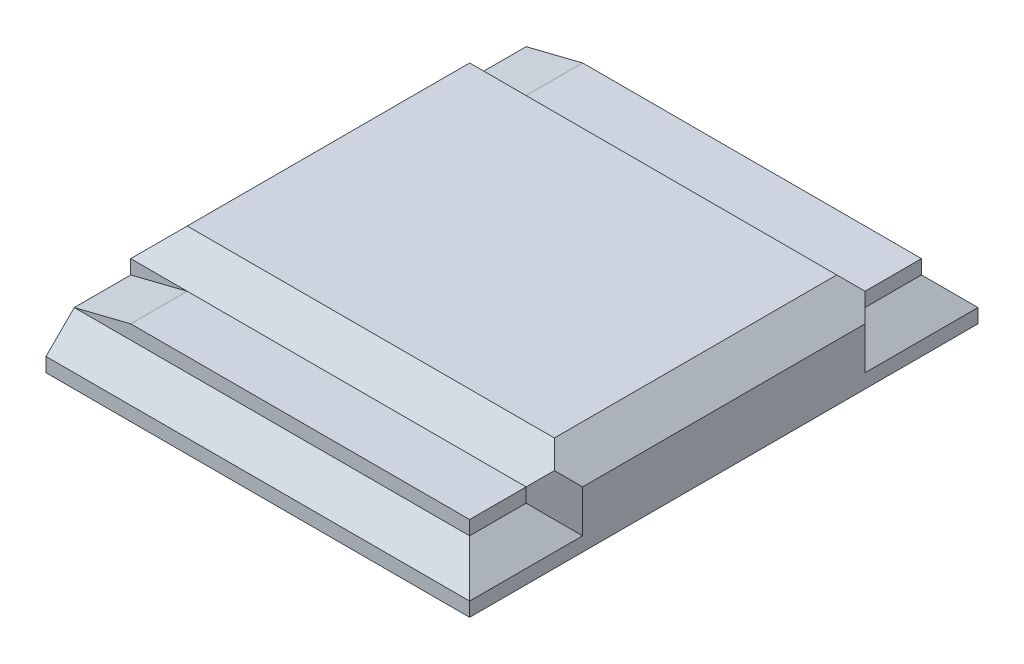
SolidWorks part; units mm, degrees
ref_plane "前视基准面" through (0, 0, 0) normal (0, 0, 1) x (1, 0, 0)
ref_plane "上视基准面" through (0, 0, 0) normal (0, 1, 0) x (1, 0, 0)
ref_plane "右视基准面" through (0, 0, 0) normal (1, 0, 0) x (0, 0, -1)
sketch "草图1" plane through (0, 0, 0) normal (0, 1, 0) x (1, 0, 0)
  line L1 (-9, -9) -> (9, -9)
  line L2 (-9, -9) -> (-9, 9)
  line L3 (-9, 9) -> (9, 9)
  line L4 (9, -9) -> (9, 9)
  line L5 (-9, -9) -> (9, 9) construction
  line L6 (-9, 9) -> (9, -9) construction
  point P0 (0, 0)
  dimension "D1" = 18
  dimension "D2" = 18
extrude "凸台-拉伸1" add sketch "草图1" along normal blind 1.5
chamfer "倒角1" distance 1 angle 45 2 edges at (0, 1.5, -9) (0, 1.5, 9)
sketch "草图2" plane through (0, 1.5, 0) normal (0, 1, 0) x (1, 0, 0)
  line L0 (-9, 8) -> (-9, -8) construction
  line L1 (9, -6) -> (-9, -6)
  line L2 (9, -6) -> (9, 6)
  line L3 (9, 6) -> (-9, 6)
  line L4 (-9, -6) -> (-9, 6)
  line L5 (9, -6) -> (-9, 6) construction
  line L6 (9, 6) -> (-9, -6) construction
  point P0 (0, 0)
  dimension "D1" = 12
extrude "凸台-拉伸2" add sketch "草图2" along normal blind 1.5
chamfer "倒角2" distance 1 angle 45 2 edges at (0, 3, -6) (0, 3, 6)
chamfer "倒角3" distance 1 angle 45 5 edges at (9, 1.75, 6) (9, 1.5, 7) (9, 1.75, -6) (9, 1.5, -7) (9, 3, 0)
sketch "草图9" plane through (-9, 0, 0) normal (-1, 0, 0) x (0, 0, 1)
  line L0 (-6, 1.5) -> (-6, 2)
  line L1 (-6, 2) -> (-5, 3)
  line L2 (-5, 3) -> (5, 3)
  line L3 (5, 3) -> (6, 2)
  line L4 (6, 2) -> (6, 1.5)
  line L5 (6, 1.5) -> (-6, 1.5)
extrude "切除-拉伸2" cut sketch "草图9" against normal blind 3
chamfer "倒角5" distance 1 angle 45 1 edges at (-6, 3, 0)
sketch "草图23" plane through (-9, 0, 0) normal (-1, 0, 0) x (0, 0, 1)
  line L6 (9, 0.5) -> (8, 1.5)
  line L7 (8, 1.5) -> (-8, 1.5)
  line L8 (-8, 1.5) -> (-9, 0.5)
  line L9 (-9, 0.5) -> (-9, 0)
  line L10 (-9, 0) -> (9, 0)
  line L11 (9, 0) -> (9, 0.5)
  line L12 (9, 0.5) -> (8, 1.5)
  line L13 (8, 1.5) -> (-8, 1.5)
  line L14 (-8, 1.5) -> (-9, 0.5)
  line L15 (-9, 0.5) -> (-9, 0)
  line L16 (-9, 0) -> (9, 0)
  line L17 (9, 0) -> (9, 0.5)
  dimension "D1" = 0
extrude "切除-拉伸5" cut sketch "草图23" against normal blind 3
sketch "草图24" plane through (0, 0, -6) normal (0, 0, -1) x (-1, 0, 0)
  line L0 (6, 1.5) -> (4, 2)
  line L1 (6, 2) -> (-8, 2) construction
  line L2 (4, 2) -> (-8, 2)
  line L3 (-8, 2) -> (-8, 1.5)
  line L5 (-8, 1.5) -> (6, 1.5)
  line L6 (-8, 2) -> (-8, 1.5) construction
  point P5 (0, 0)
  point P8 (-8, 2)
  point P10 (0, 0)
extrude "凸台-拉伸12" add sketch "草图24" along normal blind 2
sketch "草图25" plane through (0, 0, 6) normal (0, 0, 1) x (1, 0, 0)
  line L0 (-6, 1.5) -> (-4, 2)
  line L1 (8, 2) -> (-6, 2) construction
  line L2 (-4, 2) -> (8, 2)
  line L3 (8, 2) -> (8, 1.5)
  line L5 (8, 1.5) -> (-6, 1.5)
  line L7 (8, 1.5) -> (8, 2) construction
  point P6 (1, 1.5)
  point P8 (1, 1.5)
  point P9 (0, 0)
  point P10 (1, 1.5)
  point P11 (8, 2)
  point P12 (1, 2)
  point P13 (0, 0)
extrude "凸台-拉伸13" add sketch "草图25" along normal blind 2
